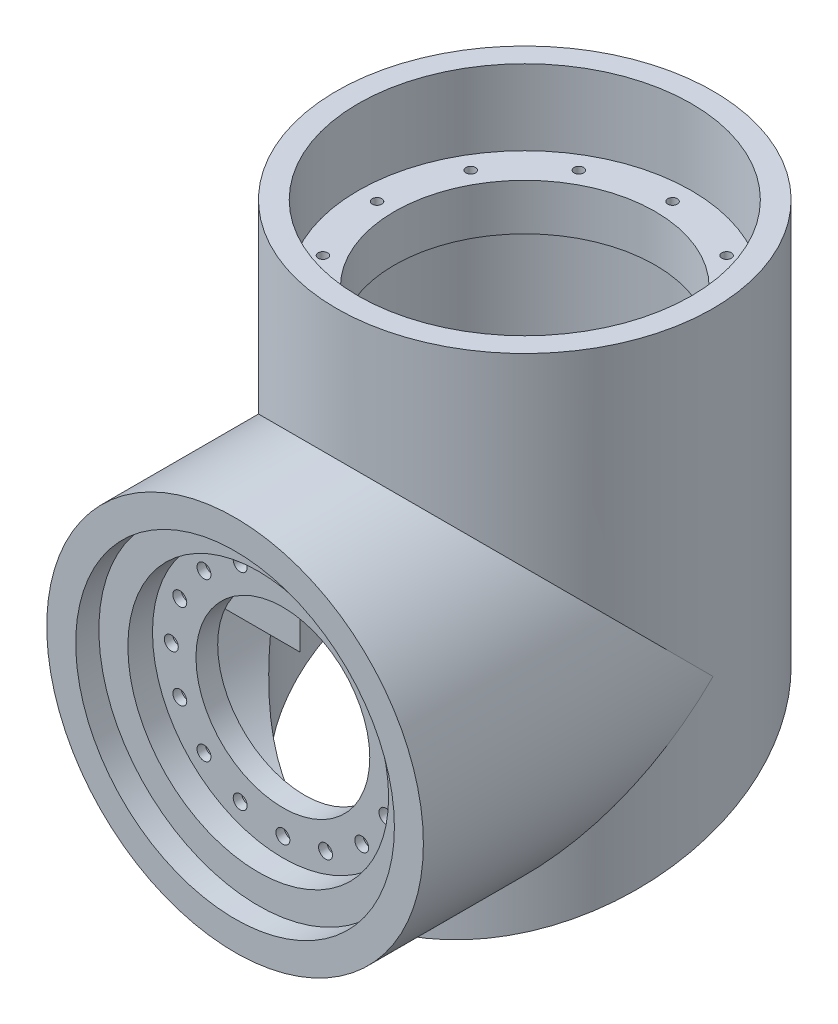
SolidWorks part; units mm, degrees
ref_plane "前视基准面" through (0, 0, 0) normal (0, 0, 1) x (1, 0, 0)
ref_plane "上视基准面" through (0, 0, 0) normal (0, 1, 0) x (1, 0, 0)
ref_plane "右视基准面" through (0, 0, 0) normal (1, 0, 0) x (0, 0, -1)
sketch "草图1" plane through (0, 0, 0) normal (0, 0, 1) x (1, 0, 0)
  circle A0 centre (0, 0) radius 65
  dimension "D1" = 130
extrude "凸台-拉伸1" add sketch "草图1" along normal blind 100
sketch "草图2" plane through (0, 0, 0) normal (0, 1, 0) x (1, 0, 0)
  circle A0 centre (0, 0) radius 65
  dimension "D1" = 130
extrude "凸台-拉伸2" add sketch "草图2" along normal blind 110 and the other way blind 70
sketch "草图4" plane through (0, 110, 0) normal (0, 1, 0) x (1, 0, 0)
  circle A0 centre (0, 0) radius 45
  dimension "D1" = 90
extrude "切除-拉伸2" cut sketch "草图4" against normal through all
sketch "草图5" plane through (0, 110, 0) normal (0, 1, 0) x (1, 0, 0)
  circle A0 centre (0, 0) radius 57.5
  dimension "D1" = 115
extrude "切除-拉伸3" cut sketch "草图5" against normal blind 26
hole_wizard "M4 螺纹孔1" positions "草图8" profile "草图7" tap size "M4" standard "GB"
sketch "草图8" plane through (0, 84, 0) normal (0, 1, 0) x (1, 0, 0)
  line L0 (0, 0) -> (0, 70.3126) construction
  circle A0 centre (0, 0) radius 51 construction
  point P0 (0, 51)
  dimension "D1" = 102
sketch "草图7" plane through (0, 84, -51) normal (1, 0, 0) x (0, 0, 1)
  line L0 (0, 0) -> (0, 7.5914)
  line L1 (0, 7.5914) -> (1.65, 6.6)
  line L2 (1.65, 6.6) -> (1.65, 0)
  line L5 (1.65, 0) -> (0, 0)
  line L10 (0, 7.5914) -> (-1.65, 6.6) construction
  line L11 (0, -6.35) -> (0, 107.95) construction
  dimension "螺纹孔钻头直径" = 3.3
  dimension "螺纹孔钻头深度" = 6.6
  dimension "导头角度" = 118
cosmetic thread "孔螺蚊线1" parameters "D1"=4.5, "D2"=4
ref_axis "基准轴1" through (0, -70, 0) along (0, 1, 0)
pattern_circular "阵列(圆周)1" count 12 over 360 about axis through (0, -70, 0) along (0, 1, 0) of "M4 螺纹孔1"
sketch "草图9" plane through (0, -70, 0) normal (0, -1, 0) x (1, 0, 0)
  circle A0 centre (0, 0) radius 55
  dimension "D1" = 110
extrude "切除-拉伸4" cut sketch "草图9" against normal blind 138
sketch "草图10" plane through (0, -70, 0) normal (0, -1, 0) x (1, 0, 0)
  circle A0 centre (0, 0) radius 62.5
  dimension "D1" = 125
extrude "切除-拉伸5" cut sketch "草图10" against normal offset from surface (76 mm away) 62 contours A0 up to face at (0, 68, -55)
hole_wizard "M4 螺纹孔2" positions "草图12" profile "草图11" tap size "M4" standard "GB"
sketch "草图12" plane through (0, 6, 0) normal (0, -1, 0) x (-1, 0, 0)
  line L0 (0, 0) -> (0, 69.1649) construction
  circle A0 centre (0, 0) radius 57 construction
  point P0 (0, 57)
  dimension "D1" = 114
sketch "草图11" plane through (0, 6, -57) normal (1, 0, 0) x (0, 0, -1)
  line L0 (0, 0) -> (0, 7.5914)
  line L1 (0, 7.5914) -> (1.65, 6.6)
  line L2 (1.65, 6.6) -> (1.65, 0)
  line L5 (1.65, 0) -> (0, 0)
  line L10 (0, 7.5914) -> (-1.65, 6.6) construction
  line L11 (0, -6.35) -> (0, 107.95) construction
  dimension "螺纹孔钻头直径" = 3.3
  dimension "螺纹孔钻头深度" = 6.6
  dimension "导头角度" = 118
cosmetic thread "孔螺蚊线2" parameters "D1"=4.5, "D2"=4
pattern_circular "阵列(圆周)2" count 12 over 360 about axis through (0, -70, 0) along (0, 1, 0) of "M4 螺纹孔2"
sketch "草图13" plane through (0, 0, 0) normal (1, 0, 0) x (0, 0, -1)
  line L0 (-65, -70) -> (65, -70)
  line L1 (65, -70) -> (65, -22.6839)
  line L2 (65, -70) -> (65, 110) construction
  line L3 (65, -22.6839) -> (-65, -70)
  dimension "D1" = 20
extrude "切除-拉伸6" cut sketch "草图13" against normal through all and the other way through all
ref_plane "基准面2" through (0, -70, 0) normal (0, 1, 0) x (1, 0, 0)
sketch "草图14" plane through (0, -70, 0) normal (0, 1, 0) x (1, 0, 0)
  line L0 (0, 0) -> (0, -133.3209) construction
  circle A0 centre (0, 0) radius 63.75 construction
  circle A1 centre (0, -63.75) radius 0.75
  dimension "D1" = 127.5
  dimension "D2" = 1.5
extrude "切除-拉伸7" cut sketch "草图14" along normal blind 5
sketch "草图15" plane through (0, -70, 0) normal (0, 1, 0) x (1, 0, 0)
  line L0 (0, 0) -> (0, 112.4929) construction
  circle A0 centre (0, 0) radius 63.75 construction
  circle A1 centre (0, 63.75) radius 0.75
  dimension "D1" = 127.5
  dimension "D2" = 1.5
extrude "切除-拉伸8" cut sketch "草图15" along normal blind 52 contours A1
sketch "草图16" plane through (0, -70, 0) normal (0, 1, 0) x (1, 0, 0)
  line L0 (0, 0) -> (85.0191, 0) construction
  line L1 (0, 0) -> (-69.3013, 0) construction
  circle A0 centre (0, 0) radius 63.75 construction
  circle A1 centre (63.75, 0) radius 0.75
  circle A2 centre (-63.75, 0) radius 0.75
  dimension "D1" = 127.5
  dimension "D2" = 1.5
  dimension "D3" = 1.5
extrude "切除-拉伸9" cut sketch "草图16" along normal blind 26
sketch "草图17" plane through (0, 0, 100) normal (0, 0, 1) x (1, 0, 0)
  circle A0 centre (0, 0) radius 55
  dimension "D1" = 110
extrude "切除-拉伸10" cut sketch "草图17" against normal blind 8 contours A0
sketch "草图18" plane through (0, 0, 92) normal (0, 0, 1) x (1, 0, 0)
  circle A0 centre (0, 0) radius 45
  dimension "D1" = 90
extrude "切除-拉伸11" cut sketch "草图18" against normal blind 8.5
sketch "草图19" plane through (0, 0, 83.5) normal (0, 0, 1) x (1, 0, 0)
  circle A0 centre (0, 0) radius 30
  dimension "D1" = 60
extrude "切除-拉伸12" cut sketch "草图19" against normal blind 8.5
sketch "草图20" plane through (0, 0, 0) normal (1, 0, 0) x (0, 0, -1)
  line L0 (-154.1809, 0) -> (89.6872, 0) construction
  line L1 (-100, 65) -> (-100, -65) construction
  line L2 (-76, 0) -> (-60, 0)
  line L3 (-76, 0) -> (-76, 55)
  line L4 (-76, 55) -> (-60, 55)
  line L5 (-60, 0) -> (-60, 55)
  dimension "D1" = 24
  dimension "D2" = 16
  dimension "D3" = 55
revolve "切除-旋转1" cut sketch "草图20" angle 360 about L0
sketch "草图21" plane through (0, 0, 60) normal (0, 0, 1) x (1, 0, 0)
  line L0 (-54.8544, -4) -> (54.8544, -4)
  line L1 (0, 0) -> (0, -78.6449) construction
  arc A0 (-54.8544, -4) -> (54.8544, -4) centre (0, 0) ccw
  dimension "D1" = 110
  dimension "D2" = 4
extrude "切除-拉伸13" cut sketch "草图21" against normal blind 50 contours L0 A0
hole_wizard "打孔尺寸(%根据)内六角圆柱头螺钉的类型1" positions "草图26" profile "草图25" counterbore size "M4" standard "GB" end condition through all
sketch "草图26" plane through (0, 0, 76) normal (0, 0, -1) x (-1, 0, 0)
  line L0 (0, 0) -> (0, -80.425) construction
  circle A0 centre (0, 0) radius 38.5 construction
  point P0 (0, -38.5)
  dimension "D1" = 77
sketch "草图25" plane through (0, -38.5, 76) normal (1, 0, 0) x (0, 1, 0)
  line L0 (0, 0) -> (0, 24)
  line L1 (0, 24) -> (2.4, 24)
  line L3 (2.4, 24) -> (2.4, 4.6)
  line L4 (2.4, 4.6) -> (4, 4.6)
  line L5 (4, 4.6) -> (4, 0)
  line L7 (4, 0) -> (0, 0)
  line L11 (0, -6.35) -> (0, 107.95) construction
  dimension "通孔孔直径" = 4.8
  dimension "通孔孔深度" = 24
  dimension "柱形沉头孔直径" = 8
  dimension "柱形沉头孔深度" = 4.6
ref_axis "基准轴2" through (0, 0, 100) along (0, 0, -1)
pattern_circular "阵列(圆周)3" count 16 over 360 about axis through (0, 0, 100) along (0, 0, -1) of "打孔尺寸(%根据)内六角圆柱头螺钉的类型1"
